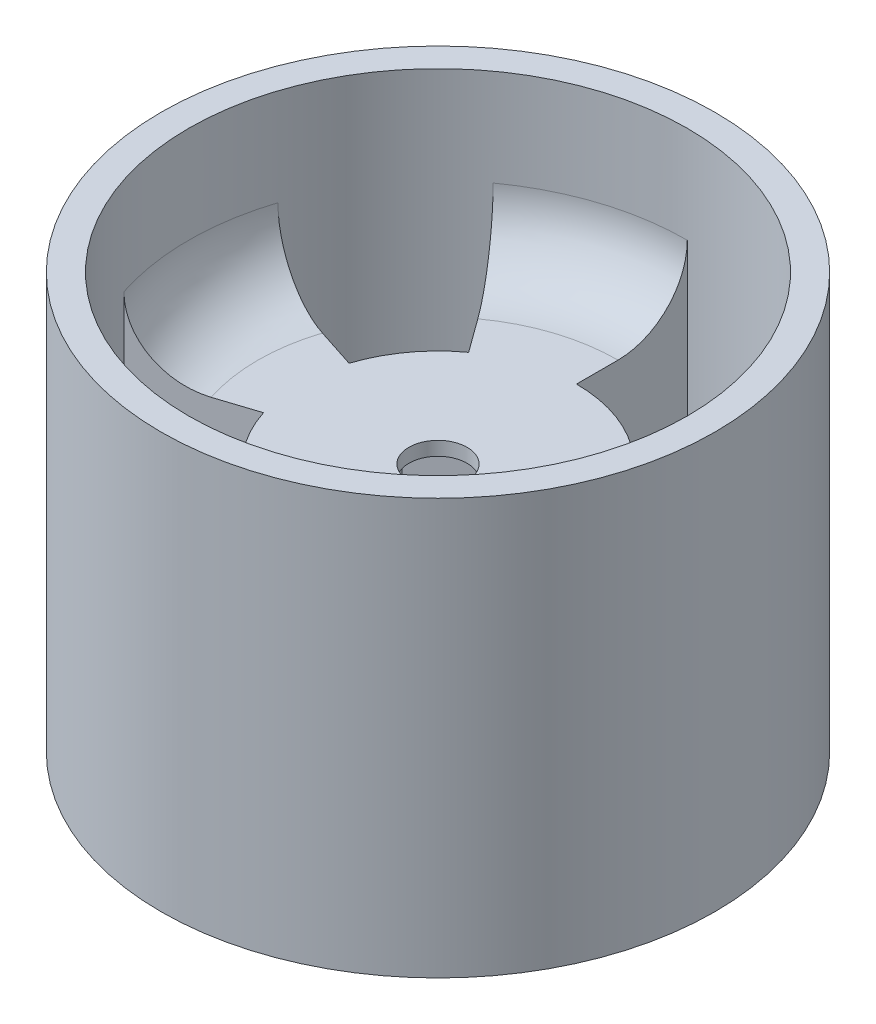
SolidWorks part; units mm, degrees
ref_plane "Front Plane" through (0, 0, 0) normal (0, 0, 1) x (1, 0, 0)
ref_plane "Top Plane" through (0, 0, 0) normal (0, 1, 0) x (1, 0, 0)
ref_plane "Right Plane" through (0, 0, 0) normal (1, 0, 0) x (0, 0, -1)
sketch "Sketch1" plane through (0, 0, 0) normal (0, 1, 0) x (1, 0, 0)
  line L1 (0, -7.1014) -> (6.15, -3.5507)
  line L2 (6.15, -3.5507) -> (6.15, 3.5507)
  line L3 (6.15, 3.5507) -> (0, 7.1014)
  line L4 (0, 7.1014) -> (-6.15, 3.5507)
  line L5 (-6.15, 3.5507) -> (-6.15, -3.5507)
  line L6 (-6.15, -3.5507) -> (0, -7.1014)
  circle A0 centre (0, 0) radius 20
  circle A1 centre (0, 0) radius 18
  circle A2 centre (0, 0) radius 2.1
  circle A3 centre (0, 0) radius 6.15 construction
extrude "Boss-Extrude1" add sketch "Sketch1" along normal blind 6 contours A1
extrude "Cut-Extrude1" cut sketch "Sketch1<27>" along normal blind 5 contours L6 L1 L2 L3 L4 L5
sketch "Sketch1<27>" plane through (0, 0, 0) normal (0, 1, 0) x (1, 0, 0) same geometry as "Sketch1"
extrude "Cut-Extrude2" cut sketch "Sketch1<28>" along normal through all contours A2
sketch "Sketch1<28>" plane through (0, 0, 0) normal (0, 1, 0) x (1, 0, 0) same geometry as "Sketch1"
extrude "Boss-Extrude2" add sketch "Sketch1<29>" along normal blind 18 contours A1 | A0
sketch "Sketch1<29>" plane through (0, 0, 0) normal (0, 1, 0) x (1, 0, 0) same geometry as "Sketch1"
sketch "Sketch2" plane through (0, 0, 0) normal (0, -1, 0) x (1, 0, 0)
  line L0 (0, -10) -> (0, -18)
  line L1 (5.8779, -8.0902) -> (10.5801, -14.5623)
  line L2 (9.5106, -3.0902) -> (17.119, -5.5623)
  line L3 (9.5106, 3.0902) -> (17.119, 5.5623)
  line L4 (5.8779, 8.0902) -> (10.5801, 14.5623)
  line L5 (0, 10) -> (0, 18)
  line L6 (-5.8779, 8.0902) -> (-10.5801, 14.5623)
  line L7 (-9.5106, 3.0902) -> (-17.119, 5.5623)
  line L8 (-9.5106, -3.0902) -> (-17.119, -5.5623)
  line L9 (-5.8779, -8.0902) -> (-10.5801, -14.5623)
  circle A0 centre (0, 0) radius 10
  circle A1 centre (0, 0) radius 18
extrude "Cut-Extrude3" cut sketch "Sketch2" against normal blind 10 contours A1 A0 | A1 A0 | A1 A0 | A1 A0 | A1 A0 region at (4.3712, 0, -13.4532) region at (-11.444, 0, -8.3146) region at (14.1456, 0, 0) region at (-11.444, 0, 8.3146) region at (4.3712, 0, 13.4532)
extrude "Boss-Extrude3" add sketch "Sketch1<30>" against normal blind 12 contours A0 A1 region at (-19.4343, 0, 0)
sketch "Sketch1<30>" plane through (0, 0, 0) normal (0, 1, 0) x (1, 0, 0) same geometry as "Sketch1"
fillet "Fillet1" radius 5 10 edges at (-18, 6, 0) (-5.5623, 6, 17.119) (14.5623, 6, 10.5801) (-5.5623, 6, -17.119) (14.5623, 6, -10.5801) (14.5623, 0, -10.5801) (-5.5623, 0, -17.119) (-18, 0, 0) (-5.5623, 0, 17.119) (14.5623, 0, 10.5801)
